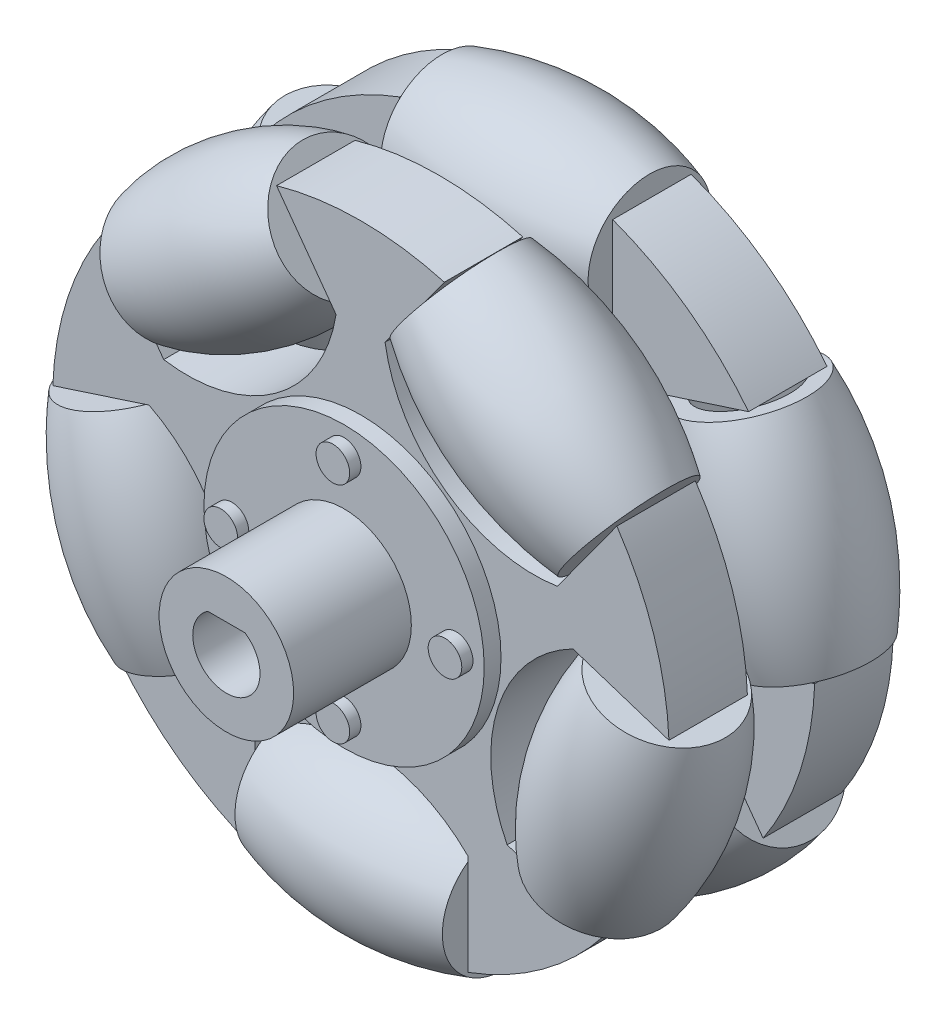
SolidWorks part; units mm, degrees
ref_plane "Front Plane" through (0, 0, 0) normal (0, 0, 1) x (1, 0, 0)
ref_plane "Top Plane" through (0, 0, 0) normal (0, 1, 0) x (1, 0, 0)
ref_plane "Right Plane" through (0, 0, 0) normal (1, 0, 0) x (0, 0, -1)
sketch "Sketch1" plane through (0, 0, 0) normal (0, 0, 1) x (1, 0, 0)
  line L0 (28.9984, -0.3039) -> (23.7817, -1.9989)
  line L2 (-9.25, 27.4852) -> (-9.25, 22)
  line L4 (9.25, 27.4852) -> (9.25, 22)
  line L5 (18.0648, 15.5956) -> (23.7817, -1.9989)
  line L6 (23.2816, 17.2907) -> (18.0648, 15.5956)
  line L7 (-9.25, 22) -> (9.25, 22)
  line L8 (8.672, -27.673) -> (5.4479, -23.2354)
  line L9 (20.4147, -12.3614) -> (5.4479, -23.2354)
  line L10 (23.6388, -16.799) -> (20.4147, -12.3614)
  line L11 (-23.6388, -16.799) -> (-20.4147, -12.3614)
  line L12 (-5.4479, -23.2354) -> (-20.4147, -12.3614)
  line L13 (-8.672, -27.673) -> (-5.4479, -23.2354)
  line L14 (-23.2816, 17.2907) -> (-18.0648, 15.5956)
  line L15 (-23.7817, -1.9989) -> (-18.0648, 15.5956)
  line L16 (-28.9984, -0.3039) -> (-23.7817, -1.9989)
  line L17 (-9.5378, 25.793) -> (-9.5378, 16.793)
  line L19 (9.4622, 16.793) -> (9.4622, 25.8208)
  line L20 (21.5833, 17.0414) -> (13.0238, 14.2603)
  line L22 (18.8951, -3.8098) -> (27.4811, -1.0201)
  line L23 (22.877, -15.2609) -> (17.5869, -7.9797)
  line L25 (2.2156, -19.1476) -> (7.522, -26.4513)
  line L26 (-7.4446, -26.4732) -> (-2.1545, -19.192)
  line L28 (-17.5258, -8.0241) -> (-22.8322, -15.3277)
  line L29 (-27.478, -1.1005) -> (-18.9185, -3.8816)
  line L31 (-13.0471, 14.1885) -> (-21.6331, 16.9782)
  circle A0 centre (0, 0) radius 29 construction
  arc A1 (-9.25, 27.4852) -> (9.25, 27.4852) centre (0, 0) cw
  arc A2 (23.2816, 17.2907) -> (28.9984, -0.3039) centre (0, 0) cw
  arc A3 (23.6388, -16.799) -> (8.672, -27.673) centre (0, 0) cw
  arc A4 (-8.672, -27.673) -> (-23.6388, -16.799) centre (0, 0) cw
  arc A5 (-28.9984, -0.3039) -> (-23.2816, 17.2907) centre (0, 0) cw
  circle A9 centre (0, 0) radius 27.5
  circle A10 centre (0, 0) radius 27.5 construction
  arc A11 (-21.6331, 16.9782) -> (-9.5378, 25.793) centre (0, 0) cw
  arc A12 (9.4622, 25.8208) -> (21.5833, 17.0414) centre (0, 0) cw
  arc A13 (27.4811, -1.0201) -> (22.877, -15.2609) centre (0, 0) cw
  arc A14 (-7.4446, -26.4732) -> (7.522, -26.4513) centre (0, 0) ccw
  arc A15 (-22.8322, -15.3277) -> (-27.478, -1.1005) centre (0, 0) cw
  arc A16 (-9.5378, 16.793) -> (9.4622, 16.793) centre (-0.0378, 26.293) ccw
  arc A17 (-13.0471, 14.1885) -> (-18.9185, -3.8816) centre (-25.0178, 8.0891) cw
  arc A18 (13.0238, 14.2603) -> (18.8951, -3.8098) centre (24.9945, 8.1609) ccw
  arc A19 (17.5869, -7.9797) -> (2.2156, -19.1476) centre (15.4852, -21.2493) ccw
  arc A20 (-2.1545, -19.192) -> (-17.5258, -8.0241) centre (-15.4241, -21.2937) ccw
  point P3 (0, 26.2962)
  point P28 (0, 0)
  point P53 (0, 0)
  dimension "D1" = 58
  dimension "D2" = 5
  dimension "D3" = 0
  dimension "D4" = 9
  dimension "D5" = 19
  dimension "D6" = 5
revolve "Revolve3" add sketch "Sketch1" angle 360 about L5 region at (26.3714, 8.5686, 0)
revolve "Revolve4" add sketch "Sketch1<6>" angle 360 about L7
sketch "Sketch1<6>" plane through (0, 0, 0) normal (0, 0, 1) x (1, 0, 0) same geometry as "Sketch1"
revolve "Revolve5" add sketch "Sketch1<7>" angle 360 about L15
sketch "Sketch1<7>" plane through (0, 0, 0) normal (0, 0, 1) x (1, 0, 0) same geometry as "Sketch1"
revolve "Revolve6" add sketch "Sketch1<8>" angle 360 about L12
sketch "Sketch1<8>" plane through (0, 0, 0) normal (0, 0, 1) x (1, 0, 0) same geometry as "Sketch1"
revolve "Revolve7" add sketch "Sketch1<9>" angle 360 about L9
sketch "Sketch1<9>" plane through (0, 0, 0) normal (0, 0, 1) x (1, 0, 0) same geometry as "Sketch1"
extrude "Boss-Extrude2" add sketch "Sketch1<10>" along normal mid plane 7 contours A20 L26 A9 L25 A19 L23 L22 A18 L20 L19 A16 L17 L31 A17 L29 L28 region at (0, 0, 0)
sketch "Sketch1<10>" plane through (0, 0, 0) normal (0, 0, 1) x (1, 0, 0) same geometry as "Sketch1"
ref_plane "Plane1" through (0, 0, 13) normal (0, 0, 1) x (1, 0, 0)
sketch "Sketch3" plane through (0, 0, 13) normal (0, 0, 1) x (1, 0, 0)
  line L0 (23.6388, 16.799) -> (20.4147, 12.3614)
  line L2 (-23.6388, 16.799) -> (-20.4147, 12.3614)
  line L4 (-8.672, 27.673) -> (-5.4479, 23.2354)
  line L5 (5.4479, 23.2354) -> (20.4147, 12.3614)
  line L6 (8.672, 27.673) -> (5.4479, 23.2354)
  line L7 (-20.4147, 12.3614) -> (-5.4479, 23.2354)
  line L8 (23.2816, -17.2907) -> (18.0648, -15.5956)
  line L9 (23.7817, 1.9989) -> (18.0648, -15.5956)
  line L10 (28.9984, 0.3039) -> (23.7817, 1.9989)
  line L11 (-9.25, -27.4852) -> (-9.25, -22)
  line L12 (9.25, -22) -> (-9.25, -22)
  line L13 (9.25, -27.4852) -> (9.25, -22)
  line L14 (-28.9984, 0.3039) -> (-23.7817, 1.9989)
  line L15 (-18.0648, -15.5956) -> (-23.7817, 1.9989)
  line L16 (-23.2816, -17.2907) -> (-18.0648, -15.5956)
  line L17 (-22.877, 15.2609) -> (-17.5869, 7.9797)
  line L19 (-2.2156, 19.1476) -> (-7.522, 26.4513)
  line L20 (7.4446, 26.4732) -> (2.1545, 19.192)
  line L22 (17.5258, 8.0241) -> (22.8322, 15.3277)
  line L23 (27.478, 1.1005) -> (18.9185, 3.8816)
  line L25 (13.0471, -14.1885) -> (21.6331, -16.9782)
  line L26 (9.5378, -25.793) -> (9.5378, -16.793)
  line L28 (-9.4622, -16.793) -> (-9.4622, -25.8208)
  line L29 (-21.5833, -17.0414) -> (-13.0238, -14.2603)
  line L31 (-18.8951, 3.8098) -> (-27.4811, 1.0201)
  circle A0 centre (0, 0) radius 29 construction
  arc A1 (-23.6388, 16.799) -> (-8.672, 27.673) centre (0, 0) cw
  arc A2 (8.672, 27.673) -> (23.6388, 16.799) centre (0, 0) cw
  arc A3 (28.9984, 0.3039) -> (23.2816, -17.2907) centre (0, 0) cw
  arc A4 (9.25, -27.4852) -> (-9.25, -27.4852) centre (0, 0) cw
  arc A5 (-23.2816, -17.2907) -> (-28.9984, 0.3039) centre (0, 0) cw
  circle A9 centre (0, 0) radius 27.5
  circle A10 centre (0, 0) radius 27.5 construction
  arc A11 (-27.4811, 1.0201) -> (-22.877, 15.2609) centre (0, 0) cw
  arc A12 (-7.522, 26.4513) -> (7.4446, 26.4732) centre (0, 0) cw
  arc A13 (22.8322, 15.3277) -> (27.478, 1.1005) centre (0, 0) cw
  arc A14 (9.5378, -25.793) -> (21.6331, -16.9782) centre (0, 0) ccw
  arc A15 (-9.4622, -25.8208) -> (-21.5833, -17.0414) centre (0, 0) cw
  arc A16 (-17.5869, 7.9797) -> (-2.2156, 19.1476) centre (-15.4852, 21.2493) ccw
  arc A17 (-18.8951, 3.8098) -> (-13.0238, -14.2603) centre (-24.9945, -8.1609) cw
  arc A18 (2.1545, 19.192) -> (17.5258, 8.0241) centre (15.4241, 21.2937) ccw
  arc A19 (18.9185, 3.8816) -> (13.0471, -14.1885) centre (25.0178, -8.0891) ccw
  arc A20 (9.5378, -16.793) -> (-9.4622, -16.793) centre (0.0378, -26.293) ccw
  circle A27 centre (0, 0) radius 12.5
  circle A28 centre (0, 0) radius 10 construction
  circle A29 centre (0, 10) radius 1.5
  circle A30 centre (0, 0) radius 10 construction
  circle A31 centre (10, 0) radius 1.5
  circle A32 centre (0, 0) radius 10 construction
  circle A33 centre (0, -10) radius 1.5
  circle A34 centre (0, 0) radius 10 construction
  circle A35 centre (-10, 0) radius 1.5
  point P3 (0, 21.2741)
  point P28 (0, 0)
  point P53 (0, 0)
  point P73 (0, 0)
  point P75 (0, 0)
  dimension "D1" = 58
  dimension "D2" = 5
  dimension "D7" = 25
  dimension "D8" = 20
  dimension "D10" = 4
  dimension "D9" = 3
  dimension "D3" = 0
  dimension "D4" = 9
  dimension "D5" = 19
  dimension "D6" = 5
extrude "Boss-Extrude5" add sketch "Sketch3" along normal mid plane 7 separate body contours L26 A20 L28 A15 L29 A17 L31 A11 L17 A16 L19 A12 L20 A18 L22 A13 L23 A19 L25 A14
revolve "Revolve14" add sketch "Sketch3<25>" angle 360 about L5
sketch "Sketch3<25>" plane through (0, 0, 13) normal (0, 0, 1) x (1, 0, 0) same geometry as "Sketch3"
revolve "Revolve15" add sketch "Sketch3<26>" angle 360 about L9
sketch "Sketch3<26>" plane through (0, 0, 13) normal (0, 0, 1) x (1, 0, 0) same geometry as "Sketch3"
revolve "Revolve16" add sketch "Sketch3<27>" angle 360 about L7
sketch "Sketch3<27>" plane through (0, 0, 13) normal (0, 0, 1) x (1, 0, 0) same geometry as "Sketch3"
revolve "Revolve17" add sketch "Sketch3<28>" angle 360 about L15
sketch "Sketch3<28>" plane through (0, 0, 13) normal (0, 0, 1) x (1, 0, 0) same geometry as "Sketch3"
revolve "Revolve18" add sketch "Sketch3<29>" angle 360 about L12
sketch "Sketch3<29>" plane through (0, 0, 13) normal (0, 0, 1) x (1, 0, 0) same geometry as "Sketch3"
extrude "Boss-Extrude6" add sketch "Sketch3<30>" along normal blind 5 and the other way blind 1 contours A27
sketch "Sketch3<30>" plane through (0, 0, 13) normal (0, 0, 1) x (1, 0, 0) same geometry as "Sketch3"
sketch "Sketch6" plane through (0, 0, -3.5) normal (0, 0, -1) x (-1, 0, 0)
  circle A0 centre (0, 0) radius 12.5
extrude "Cut-Extrude3" cut sketch "Sketch6" against normal blind 2 contours A0
sketch "Sketch9" plane through (0, 0, -1.5) normal (0, 0, -1) x (-1, 0, 0)
  line L3 (1.6583, 2.5) -> (-1.6583, 2.5)
  arc A0 (-1.6583, 2.5) -> (1.6583, 2.5) centre (0, 0) ccw
  dimension "D1" = 6
extrude "Boss-Extrude9" add sketch "Sketch3<33>" along normal blind 6 and the other way blind 16 contours A29 | A35 | A33 | A31
sketch "Sketch3<33>" plane through (0, 0, 13) normal (0, 0, 1) x (1, 0, 0) same geometry as "Sketch3"
sketch "Sketch10" plane through (0, 0, 16.5) normal (0, 0, 1) x (1, 0, 0)
  circle A0 centre (0, 0) radius 6
  dimension "D1" = 12
extrude "Boss-Extrude10" add sketch "Sketch10" along normal blind 12
extrude "Cut-Extrude4" cut sketch "Sketch9" against normal through all both and the other way through all contours A0 L3
sketch "Sketch11" plane through (0, 0, -1.5) normal (0, 0, -1) x (-1, 0, 0)
  circle A0 centre (0, 0) radius 6
  dimension "D1" = 12
extrude "Cut-Extrude5" cut sketch "Sketch11" against normal blind 15
